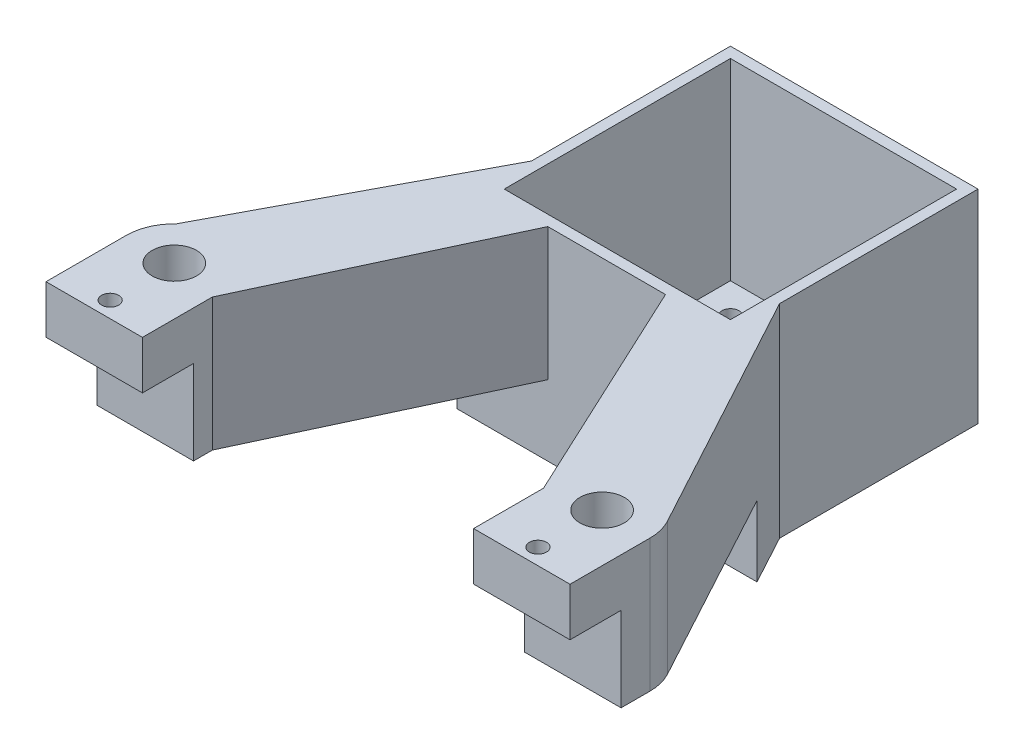
SolidWorks part; units mm, degrees
note: The reader was unsure of these and kept them because the rebuilt part matched: shared geometry of "草图7<7>", "草图7<8>".
ref_plane "前视基准面" through (0, 0, 0) normal (0, 0, 1) x (1, 0, 0)
ref_plane "上视基准面" through (0, 0, 0) normal (0, 1, 0) x (1, 0, 0)
ref_plane "右视基准面" through (0, 0, 0) normal (1, 0, 0) x (0, 0, -1)
sketch "草图6" plane through (0, 0, 0) normal (0, 1, 0) x (1, 0, 0)
  line L1 (-21.15, -21.15) -> (21.15, -21.15)
  line L2 (-21.15, -21.15) -> (-21.15, 21.15)
  line L3 (-21.15, 21.15) -> (21.15, 21.15)
  line L5 (0, 21.15) -> (0, -21.15) construction
  line L6 (-21.15, 0) -> (21.15, 0) construction
  line L8 (21.15, 21.15) -> (21.15, -21.15)
  circle A0 centre (15.5, 15.5) radius 1.6
  circle A1 centre (-15.5, 15.5) radius 1.6
  circle A2 centre (-15.5, -15.5) radius 1.6
  circle A3 centre (15.5, -15.5) radius 1.6
  circle A4 centre (0, 0) radius 15
  point P0 (0, 0)
extrude "凸台-拉伸1" add sketch "草图6" along normal blind 5
sketch "草图7" plane through (0, 5, 0) normal (0, 1, 0) x (1, 0, 0)
  line L0 (49, -65) -> (49, -79)
  line L1 (49, -79) -> (30.9639, -79)
  line L2 (21, -10) -> (47.9146, -59.7152)
  line L3 (49, -64) -> (49, -65)
  line L4 (-10, -21) -> (-30.9639, -65.9194)
  line L5 (-21, -10) -> (-46.2023, -57.4784)
  line L6 (10, -21) -> (30.9639, -65.9194)
  line L7 (30.9639, -79) -> (30.9639, -65.9194)
  line L8 (-49, -64) -> (-49, -79)
  line L9 (-30.9639, -65.9194) -> (-30.9639, -79)
  line L13 (-30.9639, -79) -> (-49, -79)
  arc A0 (-46.2023, -57.4784) -> (-49, -64) centre (-40, -64) ccw
  arc A1 (49, -64) -> (47.9146, -59.7152) centre (40, -64) ccw
  circle A2 centre (-40, -64) radius 4.15
  circle A3 centre (40, -64) radius 4.15
  circle A4 centre (40, -76) radius 1.6
  circle A5 centre (-40, -76) radius 1.6
  dimension "D1" = 18
  dimension "D2" = 18
extrude "凸台-拉伸5" add sketch "草图7" against normal blind 38
extrude "凸台-拉伸7" add sketch "草图7<7>" against normal blind 38 contours A1 A3
sketch "草图7<7>" plane through (0, 5, 0) normal (0, 1, 0) x (1, 0, 0) same geometry as "草图7"
extrude "凸台-拉伸8" add sketch "草图7<8>" against normal blind 38 contours A0 A2
sketch "草图7<8>" plane through (0, 5, 0) normal (0, 1, 0) x (1, 0, 0) same geometry as "草图7"
sketch "草图12" plane through (0, 5, 0) normal (0, 1, 0) x (1, 0, 0)
  line L0 (21.15, 21.15) -> (23.15, 21.15)
  line L1 (21.15, 21.15) -> (21.15, -23.15)
  line L2 (23.15, 21.15) -> (23.15, -23.15)
  line L3 (21.15, -23.15) -> (23.15, -23.15)
extrude "凸台-拉伸11" add sketch "草图12" against normal blind 38
sketch "草图14" plane through (0, 5, 0) normal (0, 1, 0) x (1, 0, 0)
  line L0 (21.15, -23.15) -> (-23.15, -23.15)
  line L1 (21.15, -23.15) -> (21.15, -21.15)
  line L2 (-23.15, -23.15) -> (-23.15, -21.15)
  line L3 (21.15, -21.15) -> (-23.15, -21.15)
extrude "凸台-拉伸12" add sketch "草图14" against normal blind 38
sketch "草图15" plane through (0, 5, 0) normal (0, 1, 0) x (1, 0, 0)
  line L0 (-23.15, -21.15) -> (-23.15, 21.15)
  line L1 (-23.15, -21.15) -> (-21.15, -21.15)
  line L2 (-23.15, 21.15) -> (-21.15, 21.15)
  line L3 (-21.15, -21.15) -> (-21.15, 21.15)
extrude "凸台-拉伸13" add sketch "草图15" against normal blind 38
sketch "草图17" plane through (0, -33, 0) normal (0, -1, 0) x (1, 0, 0)
  line L0 (62.0405, 30.9533) -> (62.0405, -32.0443)
  line L2 (62.0405, 30.9533) -> (62.0405, 85.063)
  line L3 (62.0405, 85.063) -> (-8.6048, 85.063)
  line L4 (62.0405, -32.0443) -> (-61.8372, -32.0443)
  line L6 (-61.8372, -32.0443) -> (-61.8372, 30.9533)
  line L7 (-8.6048, 85.063) -> (-61.8372, 85.063)
  line L8 (-61.8372, 30.9533) -> (-61.8372, 85.063)
extrude "切除-拉伸1" cut sketch "草图17" against normal blind 13.2
sketch "草图18" plane through (49, 0, 0) normal (1, 0, 0) x (0, 0, -1)
  line L0 (-79, -19.8) -> (-79, 5) construction
  line L1 (-79, -4) -> (-69.4505, -4)
  line L2 (-79, -4) -> (-79, -12.6432)
  line L4 (-69.4505, -4) -> (-69.4505, -12.6432)
  line L5 (-69.4505, -12.6432) -> (-69.4505, -19.8)
  line L6 (-64, -19.8) -> (-79, -19.8) construction
  line L7 (-69.4505, -19.8) -> (-79, -19.8)
  line L8 (-79, -19.8) -> (-79, -12.6432)
extrude "切除-拉伸2" cut sketch "草图18" against normal blind 123
sketch "草图19" plane through (0, 0, 0) normal (0, -1, 0) x (-1, 0, 0)
  line L0 (21.15, -21.15) -> (-21.15, -21.15) construction
  line L1 (-21.15, 21.15) -> (21.15, 21.15) construction
  circle A0 centre (0, -17.95) radius 1.5
  circle A1 centre (0, -17.95) radius 2.9
  circle A2 centre (0, 17.95) radius 1.5
  circle A3 centre (0, 17.95) radius 2.9
  dimension "D1" = 5.8
  dimension "D2" = 3.2
  dimension "D4" = 5.8
  dimension "D3" = 3.2
extrude "切除-拉伸3" cut sketch "草图19" against normal blind 10 contours A0 | A2
sketch "草图23" plane through (0, -19.8, 0) normal (0, -1, 0) x (-1, 0, 0)
  line L0 (-23.15, 21.15) -> (-23.15, -23.15)
  line L1 (-23.15, -23.15) -> (23.15, -23.15)
  line L2 (23.15, -23.15) -> (23.15, 21.15)
  line L3 (23.15, 21.15) -> (-23.15, 21.15)
  line L4 (-21.15, -21.15) -> (21.15, -21.15)
  line L5 (21.15, -21.15) -> (21.15, 21.15)
  line L6 (21.15, 21.15) -> (-21.15, 21.15)
  line L7 (-21.15, 21.15) -> (-21.15, -21.15)
  line L8 (-23.15, 21.15) -> (-21.15, 21.15)
  line L9 (21.15, 21.15) -> (23.15, 21.15)
  line M9 (23.15, -14.0504) -> (23.15, 21.15)
  line M10 (23.15, 21.15) -> (21.15, 21.15)
  line M11 (21.15, 21.15) -> (21.15, -21.15)
  line M12 (21.15, -21.15) -> (-21.15, -21.15)
  line M13 (-21.15, -21.15) -> (-21.15, 21.15)
  line M14 (-21.15, 21.15) -> (-23.15, 21.15)
  line M15 (-23.15, 21.15) -> (-23.15, -13.9714)
  line M22 (-11.0034, -23.15) -> (11.0034, -23.15)
extrude "凸台-拉伸15" add sketch "草图23" along normal blind 11.2 contours L1 L2 L0 M9 M10 M11 M12 M13 M14 M15 M22
sketch "草图24" plane through (0, -19.8, 0) normal (0, -1, 0) x (-1, 0, 0)
  line L0 (23.15, -23.15) -> (27.9802, -23.15)
  line L1 (23.15, -14.0504) -> (46.2023, -57.4784) construction
  line L2 (27.9802, -23.15) -> (23.15, -14.0504)
  line L3 (23.15, -14.0504) -> (23.15, -23.15)
  line L4 (-23.15, -23.15) -> (-28.1191, -23.15)
  line L5 (-23.15, -13.9714) -> (-47.9146, -59.7152) construction
  line L6 (-28.1191, -23.15) -> (-23.15, -13.9714)
  line L7 (-23.15, -13.9714) -> (-23.15, -23.15)
extrude "凸台-拉伸16" add sketch "草图24" along normal blind 11.2
sketch "草图25" plane through (0, -31, 0) normal (0, -1, 0) x (1, 0, 0)
  line L0 (28.1191, 23.15) -> (-27.9802, 23.15)
  line L1 (28.1191, 23.15) -> (-27.9802, 23.15) construction
  line L2 (-27.9802, 23.15) -> (-23.15, 14.0504)
  line L3 (-23.15, -21.15) -> (23.15, -21.15)
  line L5 (23.15, -21.15) -> (23.15, 13.9714)
  line L6 (23.15, 13.9714) -> (28.1191, 23.15)
  line L7 (-23.15, 14.0504) -> (-23.15, -21.15)
extrude "凸台-拉伸17" add sketch "草图25" along normal blind 2
sketch "草图26" plane through (0, -33, 0) normal (0, -1, 0) x (1, 0, 0)
  line L0 (0, -21.15) -> (0, 21.15) construction
  circle A0 centre (-15.5, 15.5) radius 1.6
  circle A1 centre (15.5, 15.5) radius 1.6
  circle A2 centre (15.5, -15.5) radius 1.6
  circle A3 centre (-15.5, -15.5) radius 1.6
  circle A4 centre (0, 0) radius 15
extrude "切除-拉伸10" cut sketch "草图26" against normal blind 2
sketch "草图27" plane through (0, 0, 0) normal (0, -1, 0) x (1, 0, 0)
  line L0 (-21.15, 21.15) -> (21.15, 21.15)
  line L1 (21.15, 21.15) -> (21.15, -21.15)
  line L2 (21.15, -21.15) -> (-21.15, -21.15)
  line L3 (-21.15, -21.15) -> (-21.15, 21.15)
extrude "切除-拉伸12" cut sketch "草图27" against normal blind 5
sketch "草图29" plane through (0, 0, -21.15) normal (0, 0, -1) x (-1, 0, 0)
  line L0 (23.15, -33) -> (-23.15, -33)
  line L1 (-23.15, -33) -> (-23.15, 5)
  line L2 (-23.15, 5) -> (23.15, 5)
  line L3 (23.15, 5) -> (23.15, -33)
extrude "凸台-拉伸18" add sketch "草图29" along normal blind 2
